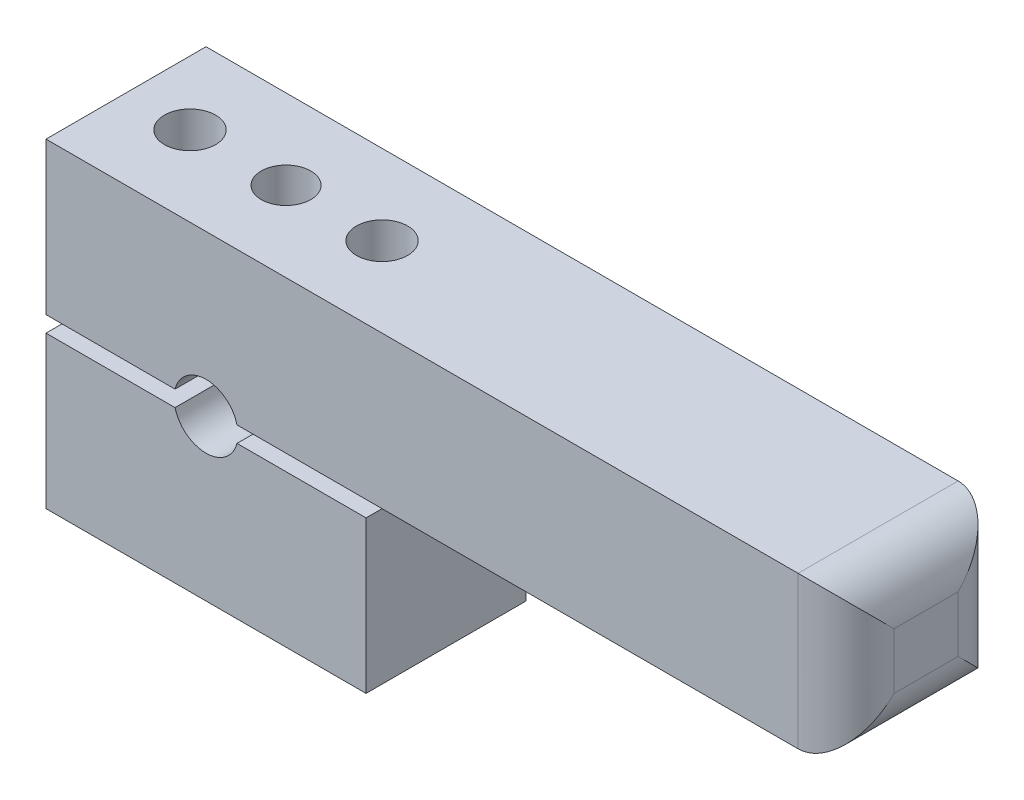
SolidWorks part; units mm, degrees
ref_plane "Front Plane" through (0, 0, 0) normal (0, 0, 1) x (1, 0, 0)
ref_plane "Top Plane" through (0, 0, 0) normal (0, 1, 0) x (1, 0, 0)
ref_plane "Right Plane" through (0, 0, 0) normal (1, 0, 0) x (0, 0, -1)
sketch "Sketch1" plane through (0, 0, 0) normal (0, 0, 1) x (1, 0, 0)
  line L1 (-10, -10) -> (10, -10)
  line L2 (-10, -10) -> (-10, 10)
  line L3 (-10, 10) -> (10, 10)
  line L4 (10, -10) -> (10, 10)
  line L5 (-10, -10) -> (10, 10) construction
  line L6 (-10, 10) -> (10, -10) construction
  line L7 (-10, -0.5) -> (-1.9365, -0.5)
  line L8 (-10, -0.5) -> (-10, 0.5)
  line L9 (-10, 0.5) -> (-1.9365, 0.5)
  line L10 (-1.9365, -0.5) -> (-1.9365, 0.5)
  line L11 (1.9365, -0.5) -> (10, -0.5)
  line L12 (1.9365, -0.5) -> (1.9365, 0.5)
  line L13 (1.9365, 0.5) -> (10, 0.5)
  line L14 (10, -0.5) -> (10, 0.5)
  circle A0 centre (0, 0) radius 2
  point P0 (0, 0)
  point P12 (1.9365, 0)
  point P13 (-1.9365, 0)
  dimension "D3" = 4
  dimension "D1" = 20
  dimension "D2" = 20
  dimension "D4" = 1
  dimension "D5" = 1
extrude "Boss-Extrude1" add sketch "Sketch1" along normal blind 10 contours A0 L7 L2 L1 L4 L11 | A0 L13 L4 L3 L2 L9 region at (0, -5.3456, 0) region at (0, 5.3456, 0)
sketch "Sketch2" plane through (0, 10, 0) normal (0, 1, 0) x (1, 0, 0)
  line L0 (0, 2.419) -> (0, -12.419) construction
  line L1 (-10, -5) -> (10, -5) construction
  line L2 (-10, 0) -> (10, 0) construction
  line L3 (10, -10) -> (10, 0) construction
  line L4 (10, 0) -> (-10, 0)
  line L5 (-10, 0) -> (-10, -10)
  line L6 (-10, -10) -> (10, -10)
  line L7 (10, -10) -> (10, 0)
  line L9 (-10, -5) -> (-10, -10)
  line L10 (-10, -10) -> (0, -10)
  circle A0 centre (-6, -5) radius 1.6
  circle A1 centre (6, -5) radius 1.6
  circle A2 centre (0, -5) radius 1.55
  point P13 (0, 0)
  point P17 (0, 0)
  dimension "D2" = 3.2
  dimension "D6" = 3.1
  dimension "D3" = 4
  dimension "D4" = 5
  dimension "D5" = 4
  dimension "D1" = 0
extrude "Cut-Extrude1" cut sketch "Sketch2" against normal through all contours A0 | A1 region at (-6, 10, 5) region at (6, 10, 5)
sketch "Sketch3" plane through (0, 10, 0) normal (0, 1, 0) x (1, 0, 0)
  line L0 (0, 4.628) -> (0, -15.1594) construction
  line L1 (-6, -5) -> (6, -5) construction
  circle A0 centre (0, -5) radius 1.55
  dimension "D1" = 3.1
extrude "Cut-Extrude2" cut sketch "Sketch3" against normal blind 10
sketch "Sketch4" plane through (0, -10, 0) normal (0, -1, 0) x (1, 0, 0)
  line L1 (-4.4123, 7.75) -> (-7.5877, 7.75)
  line L2 (-7.5877, 7.75) -> (-9.1754, 5)
  line L3 (-9.1754, 5) -> (-7.5877, 2.25)
  line L4 (-7.5877, 2.25) -> (-4.4123, 2.25)
  line L5 (-4.4123, 2.25) -> (-2.8246, 5)
  line L6 (-2.8246, 5) -> (-4.4123, 7.75)
  line L7 (7.5877, 7.75) -> (4.4123, 7.75)
  line L8 (4.4123, 7.75) -> (2.8246, 5)
  line L9 (2.8246, 5) -> (4.4123, 2.25)
  line L10 (4.4123, 2.25) -> (7.5877, 2.25)
  line L11 (7.5877, 2.25) -> (9.1754, 5)
  line L12 (9.1754, 5) -> (7.5877, 7.75)
  circle A0 centre (-6, 5) radius 2.75 construction
  circle A1 centre (6, 5) radius 2.75 construction
  dimension "D1" = 5.5
extrude "Cut-Extrude3" cut sketch "Sketch4" against normal blind 3
sketch "Sketch5" plane through (10, 0, 0) normal (1, 0, 0) x (0, 0, -1)
  line L4 (0, 0.5) -> (0, 10)
  line L5 (0, 10) -> (-10, 10)
  line L6 (-10, 10) -> (-10, 0.5)
  line L7 (-10, 0.5) -> (0, 0.5)
  line L8 (0, 0.5) -> (0, 10)
  line L9 (0, 10) -> (-10, 10)
  line L10 (-10, 10) -> (-10, 0.5)
  line L11 (-10, 0.5) -> (0, 0.5)
  dimension "D1" = 0
extrude "Boss-Extrude2" add sketch "Sketch5" along normal blind 30
fillet "Fillet1" radius 3 4 edges at (40, 5.25, 10) (40, 10, 5) (40, 5.25, 0) (40, 0.5, 5)
